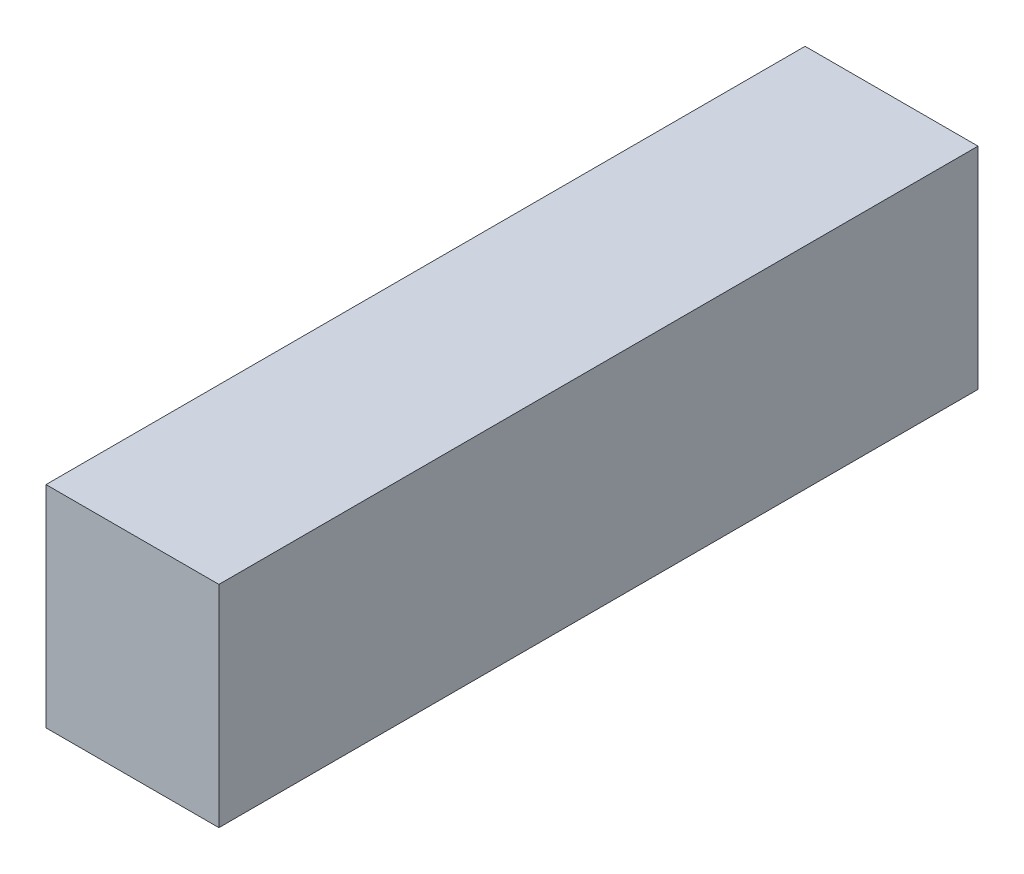
SolidWorks part; units mm, degrees
ref_plane "Front Plane" through (0, 0, 0) normal (0, 0, 1) x (1, 0, 0)
ref_plane "Top Plane" through (0, 0, 0) normal (0, 1, 0) x (1, 0, 0)
ref_plane "Right Plane" through (0, 0, 0) normal (1, 0, 0) x (0, 0, -1)
sketch "Sketch1" plane through (0, 0, 0) normal (1, 0, 0) x (0, 0, -1)
  line L1 (-48.895, 25.4386) -> (82.8131, 25.4386)
  line L2 (-48.895, 25.4386) -> (-48.895, -11.1225)
  line L3 (-48.895, -11.1225) -> (82.8131, -11.1225)
  line L4 (82.8131, 25.4386) -> (82.8131, -11.1225)
extrude "Boss-Extrude1" add sketch "Sketch1" along normal blind 30
